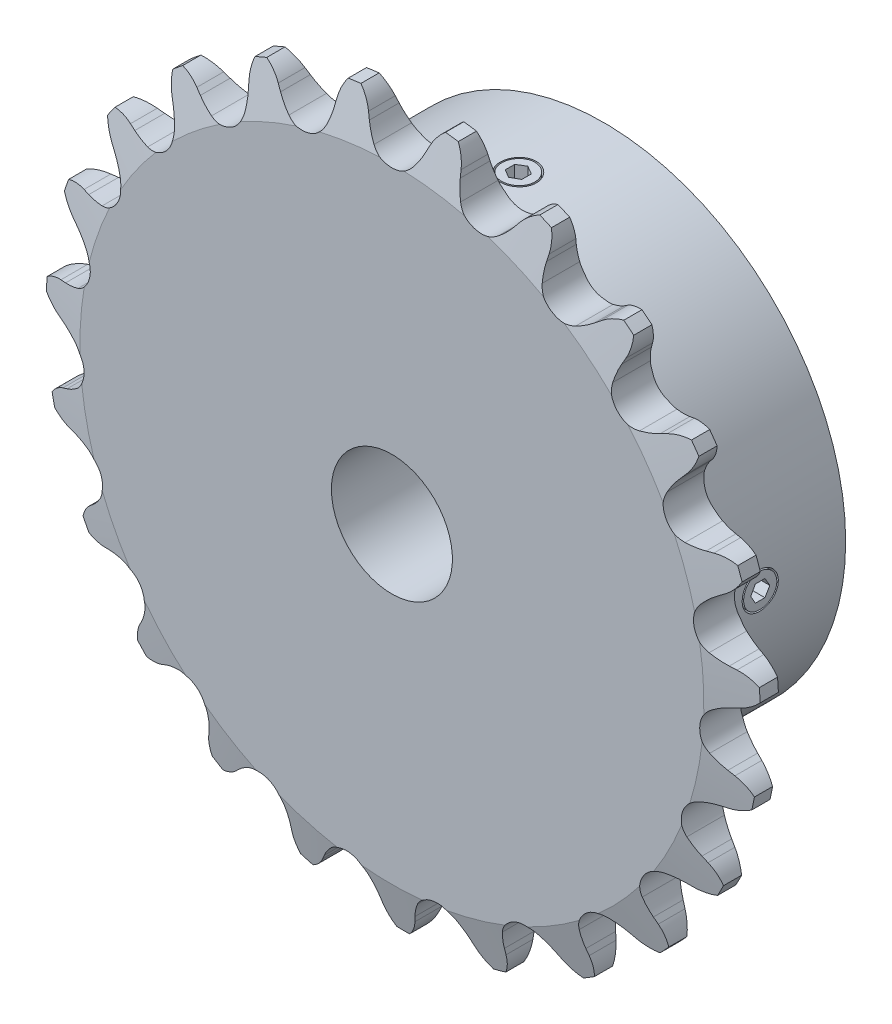
SolidWorks part; units mm, degrees
material "Plain Carbon Steel"
ref_plane "Front Plane" through (0, 0, 0) normal (0, 0, 1) x (1, 0, 0)
ref_plane "Top Plane" through (0, 0, 0) normal (0, 1, 0) x (1, 0, 0)
ref_plane "Right Plane" through (0, 0, 0) normal (1, 0, 0) x (0, 0, -1)
ref_axis "Axis1" through (0, 0, -88.99) along (0, 0, 1)
sketch "Sprocket-BaseSketch" plane through (0, 0, 0) normal (1, 0, 0) x (0, 0, -1)
  line L0 (2.1463, 0) -> (2.1463, 32.7448)
  line L1 (2.1463, 32.7448) -> (0.9557, 37.5073)
  line L2 (0.9557, 37.5073) -> (-0.9557, 37.5073)
  line L3 (-0.9557, 37.5073) -> (-2.1463, 32.7448)
  line L4 (-2.1463, 32.7448) -> (-2.1463, 0)
  line L5 (-2.1463, 0) -> (2.1463, 0)
  line L6 (8.5852, 0) -> (-2.6829, 0) construction
  dimension "Hub Surface" = 2.1463
  dimension "RightSide (1)" = 1.1906
  dimension "RightSide (2)" = 4.7625
  dimension "OD" = 37.5073
  dimension "LeftSide (1)" = 1.1906
  dimension "LeftSide (2)" = 4.7625
  dimension "Tooth Width" = 4.2926
revolve "35 (06C) ANSI (ISO) Chain Number, 2.754in P.D." add sketch "Sprocket-BaseSketch" angle 360 about L6
sketch "Tooth-Sketch" plane through (0, 0, 0) normal (0, 0, 1) x (1, 0, 0)
  line L0 (0, 0) -> (0, 46.634) construction
  line L1 (2.9488, 34.958) -> (3.1951, 35.5663)
  line L2 (-2.9488, 34.958) -> (-3.1951, 35.5663)
  line L3 (0, 34.9755) -> (9.4363, 33.6785) construction
  line L4 (0, 34.9755) -> (-9.4363, 33.6785) construction
  arc A0 (-2.0524, 33.3944) -> (2.0524, 33.3944) centre (0, 34.9755) ccw
  arc A1 (2.0524, 33.3944) -> (2.9488, 34.958) centre (-3.2195, 37.4556) ccw
  arc A2 (-2.0524, 33.3944) -> (-2.9488, 34.958) centre (3.2195, 37.4556) cw
  arc A3 (3.1951, 35.5663) -> (7.0458, 38.1614) centre (7.0458, 34.0071) cw
  arc A4 (-3.1951, 35.5663) -> (-7.0458, 38.1614) centre (-7.0458, 34.0071) ccw
  arc A5 (7.0458, 38.1614) -> (-7.0458, 38.1614) centre (0, 0) ccw
extrude "Tooth-Cut, Number of teeth: 23" cut sketch "Tooth-Sketch" against normal through all and the other way through all
pattern_circular "Tooth Pattern, 23 / 23" count 23 every 15.652 about axis through (0, 0, -88.99) along (0, 0, 1) of "Tooth-Cut, Number of teeth: 23"
sketch "Sketch3" plane through (0, 0, 0) normal (1, 0, 0) x (0, 0, -1)
  line L0 (-17.9324, 0) -> (17.9324, 0) construction
  line L1 (2.1463, 0) -> (2.1463, 25.4)
  line L2 (2.1463, 25.4) -> (20.0787, 25.4)
  line L3 (20.0787, 25.4) -> (20.0787, 0)
  line L4 (20.0787, 0) -> (2.1463, 0)
  dimension "Hub Mounting" = 2.1463
  dimension "Hub OD" = 25.4
  dimension "Hub Width" = 17.9324
revolve "Hub-Revolve1" add sketch "Sketch3" angle 360 about L0
sketch "Sketch4" plane through (0, 0, -20.0787) normal (0, 0, -1) x (-1, 0, 0)
  circle A0 centre (0, 0) radius 6.35
  dimension "Bore Diameter " = 12.7
extrude "Cut-Extrude1" cut sketch "Sketch4" against normal through all
sketch "Sketch5" plane through (0, 0, -20.0787) normal (0, 0, -1) x (-1, 0, 0)
  line L1 (-1.5875, 6.1484) -> (1.5875, 6.1484)
  line L2 (-1.5875, 6.1484) -> (-1.5875, 7.7359)
  line L3 (-1.5875, 7.7359) -> (1.5875, 7.7359)
  line L4 (1.5875, 6.1484) -> (1.5875, 7.7359)
  circle A0 centre (0, 0) radius 6.35 construction
  dimension "Keyway Wd " = 3.175
  dimension "Keyway Dp " = 1.5875
extrude "Cut-Extrude2" cut sketch "Sketch5" against normal through all
sketch "Sketch6" plane through (0, 7.7359, 0) normal (0, -1, 0) x (1, 0, 0)
  line L0 (0, -20.0787) -> (0, -2.1463) construction
  line L1 (-1.5875, -20.0787) -> (1.5875, -20.0787) construction
  line L2 (-1.2746, -2.1463) -> (1.2746, -2.1463) construction
  line L3 (-1.5875, 2.1463) -> (-1.5875, -20.0787) construction
  circle A0 centre (0, -11.1125) radius 1.5875
extrude "Cut-Extrude3" cut sketch "Sketch6" against normal through all draft 1 draft outward yes
sketch "Sketch7" plane through (0, 7.7359, 0) normal (0, -1, 0) x (1, 0, 0)
  line L0 (1.5875, -20.0787) -> (1.5875, -11.1125) construction
  line L1 (1.5875, 2.1463) -> (1.5875, -20.0787) construction
  line L2 (1.5875, -11.1125) -> (1.8946, -11.1125) construction
  line L3 (1.741, -11.1125) -> (1.741, -20.0787) construction
  line L4 (-6.35, -20.0787) -> (6.35, -20.0787) construction
  arc A0 (1.5875, -11.1125) -> (-1.5875, -11.1125) centre (0, -11.1125) ccw construction
  circle A1 centre (0, -11.1125) radius 1.741
  spline S0 degree 3 poles (-1.5309, -12.2571) (-1.2688, -12.526) (-1.1741, -12.6055) (-0.9706, -12.7453) (-0.8605, -12.8061) (-0.6322, -12.904) (-0.5145, -12.9413) (-0.2722, -12.9928) (-0.1467, -13.0067) (0.2243, -13.0112) (0.4743, -12.9645) (0.9327, -12.7811) (1.1458, -12.6424) (1.4112, -12.3835) (1.4924, -12.287) (1.6324, -12.0827) (1.6919, -11.9746) (1.7899, -11.7464) (1.8278, -11.6264) (1.879, -11.3848) (1.8928, -11.2618) (1.896, -11.0114) (1.8853, -10.888) (1.8403, -10.6451) (1.8054, -10.5244) (1.7132, -10.2935) (1.6564, -10.184) (1.5216, -9.9762) (1.4429, -9.8777) (1.1841, -9.6121) (0.9747, -9.4681) (0.5211, -9.2731) (0.2723, -9.2201) (-0.0985, -9.2152) (-0.2243, -9.2259) (-0.468, -9.2712) (-0.5866, -9.3056) (-0.8172, -9.3976) (-0.9289, -9.4556) (-1.1359, -9.5902) (-1.2326, -9.6673) (-1.4117, -9.8419) (-1.4914, -9.9368) (-1.6312, -10.1403) (-1.6919, -10.2502) (-1.7899, -10.4787) (-1.8272, -10.5964) (-1.8788, -10.8386) (-1.8928, -10.9641) (-1.8977, -11.3352) (-1.8513, -11.5852) (-1.6685, -12.0439) (-1.5309, -12.2571) (-1.2688, -12.526) (-1.1741, -12.6055) knots -0.0625 -0.0625 0 0 0.03125 0.03125 0.0625 0.0625 0.09375 0.09375 0.125 0.125 0.1875 0.1875 0.25 0.25 0.28125 0.28125 0.3125 0.3125 0.34375 0.34375 0.375 0.375 0.40625 0.40625 0.4375 0.4375 0.46875 0.46875 0.5 0.5 0.5625 0.5625 0.625 0.625 0.65625 0.65625 0.6875 0.6875 0.71875 0.71875 0.75 0.75 0.78125 0.78125 0.8125 0.8125 0.84375 0.84375 0.875 0.875 0.9375 0.9375 1 1 1.03125 1.03125 1.0625 only from (-1.3562, -12.4363) to (-1.3562, -12.4363) construction
extrude "Extrude1" add sketch "Sketch7" against normal up to surface (17.6641 mm away) up to face at (1.0215, 25.3794, -9.5159)
sketch "Sketch8" plane through (0, 7.7359, 0) normal (0, -1, 0) x (1, 0, 0)
  line L0 (0, -11.1125) -> (1.741, -11.1125) construction
  line L1 (0.8705, -11.1125) -> (0.8705, -12.6203) construction
  line L3 (0, -12.1177) -> (0.8705, -11.6151)
  line L4 (0.8705, -11.6151) -> (0.8705, -10.6099)
  line L5 (0.8705, -10.6099) -> (0, -10.1073)
  line L6 (0, -10.1073) -> (-0.8705, -10.6099)
  line L7 (-0.8705, -10.6099) -> (-0.8705, -11.6151)
  line L8 (-0.8705, -11.6151) -> (0, -12.1177)
  circle A0 centre (0, -11.1125) radius 1.741 construction
  circle A1 centre (0, -11.1125) radius 0.8705 construction
extrude "Cut-Extrude4" cut sketch "Sketch8" against normal through all from offset 2.54 offset against normal yes
pattern_circular "CirPattern1" count 2 over 90 about axis through (0, 0, 2.1463) along (0, 0, -1) of "Cut-Extrude3", "Extrude1", "Cut-Extrude4"
sketch "Sketch9" plane through (0, 0, -20.0787) normal (0, 0, -1) x (-1, 0, 0)
  line L0 (-37.5073, 0) -> (37.5073, 0)
  line L1 (-4.7625, -34.6498) -> (4.7625, -34.6498)
  line L2 (-37.5073, -2.2225) -> (37.5073, -2.2225)
  line L3 (-4.7625, -32.4273) -> (4.7625, -32.4273)
  circle A0 centre (0, 0) radius 37.5073
  circle A1 centre (0, 0) radius 6.35
  arc A2 (-1.5875, 6.1484) -> (1.5875, 6.1484) centre (0, 0) ccw construction
  arc A3 (-14.3245, 34.6642) -> (-15.5566, 34.129) centre (0, 0) ccw construction
  dimension "D1" = 2.2225
  dimension "D2" = 2.2225
sketch "Sketch10" plane through (0, 0, -20.0787) normal (0, 0, -1) x (-1, 0, 0)
  line L0 (-1.5875, 7.7359) -> (-1.5875, 6.1484) construction
  line L1 (1.5875, 7.7359) -> (-1.5875, 7.7359) construction
  line L2 (1.5875, 6.1484) -> (1.5875, 7.7359) construction
  line L3 (-1.5875, 7.7359) -> (-1.5875, 6.1484)
  line L4 (1.5875, 7.7359) -> (-1.5875, 7.7359)
  line L5 (1.5875, 6.1484) -> (1.5875, 7.7359)
  arc A0 (-1.5875, 6.1484) -> (1.5875, 6.1484) centre (0, 0) ccw construction
  arc A1 (1.5875, 6.1484) -> (-1.5875, 6.1484) centre (0, 0) ccw
extrude "Extrude2" add sketch "Sketch10" against normal up to surface (22.225 mm away) up to face at (0, 3.8175, 2.1463)
